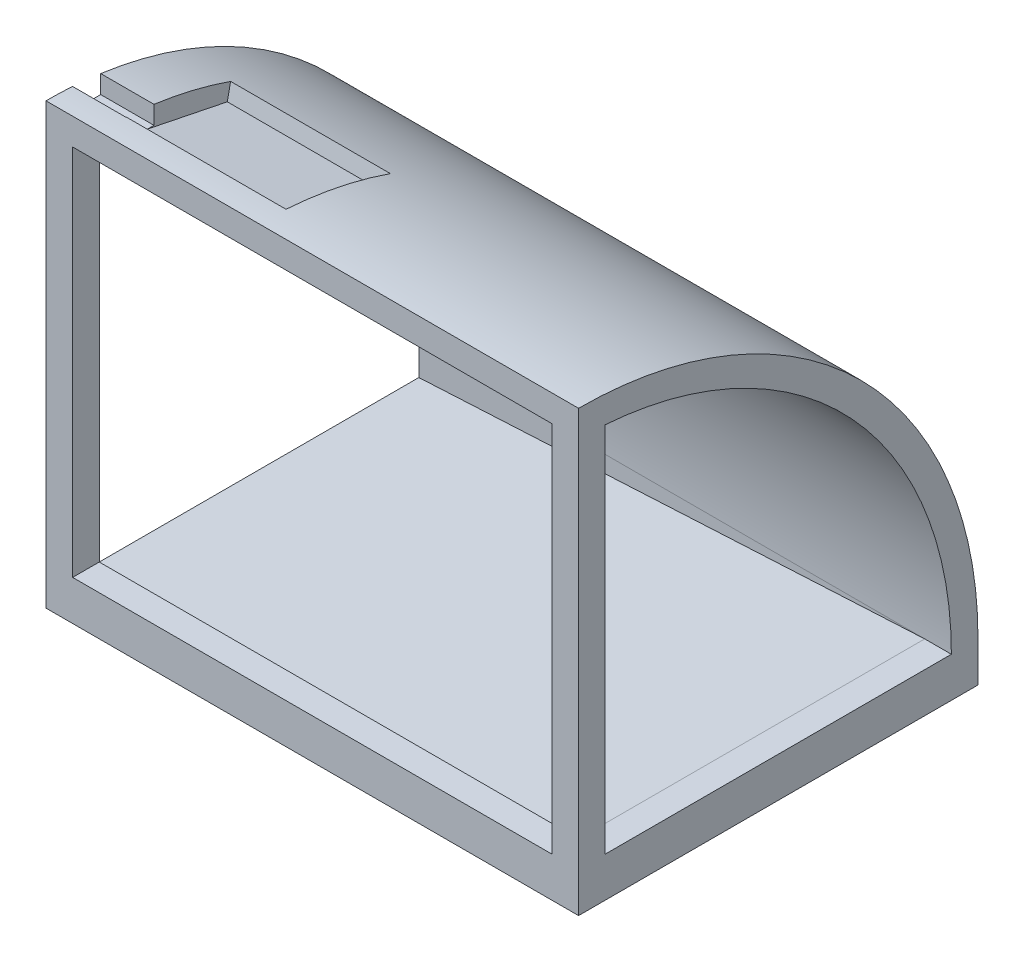
SolidWorks part; units mm, degrees
note: The reader was unsure of these and kept them because the rebuilt part matched: shared geometry of "Sketch1<5>", "Sketch1<6>".
ref_plane "Front Plane" through (0, 0, 0) normal (0, 0, 1) x (1, 0, 0)
ref_plane "Top Plane" through (0, 0, 0) normal (0, 1, 0) x (1, 0, 0)
ref_plane "Right Plane" through (0, 0, 0) normal (1, 0, 0) x (0, 0, -1)
sketch "Sketch1" plane through (0, 0, 0) normal (0, 1, 0) x (1, 0, 0)
  line L0 (-100, 65) -> (100, 65)
  line L3 (-100, 75) -> (100, 75)
  line L5 (-100, -75) -> (100, 75) construction
  line L6 (-100, 75) -> (100, -75) construction
  line L7 (-100, 75) -> (-100, 65)
  line L8 (100, 65) -> (100, 75)
  line L9 (-100, -15) -> (100, -15) construction
  line L10 (-100, 65) -> (100, 65)
  line L11 (-100, 65) -> (-100, -75)
  line L12 (-100, -75) -> (100, -75)
  line L13 (100, 65) -> (100, -75)
  line L14 (-100, -75) -> (-90, -75)
  line L15 (-100, -75) -> (-100, -65)
  line L16 (-100, -65) -> (-90, -65)
  line L17 (-90, -75) -> (-90, -65)
  line L18 (100, -75) -> (90, -75)
  line L19 (100, -75) -> (100, -65)
  line L20 (100, -65) -> (90, -65)
  line L21 (90, -75) -> (90, -65)
  point P0 (0, 0)
  dimension "D1" = 200
  dimension "D2" = 150
  dimension "D3" = 10
  dimension "D4" = 10
  dimension "D5" = 60
extrude "Boss-Extrude1" add sketch "Sketch1" against normal blind 15 contours L13 L0 L11 L12 | L0 L8 L3 L7 | L15 L14 L17 L16 | L19 L18 L21 L20
revolve "Revolve1" add sketch "Sketch1<5>" angle 90 about L12
sketch "Sketch1<5>" plane through (0, 0, 0) normal (0, 1, 0) x (1, 0, 0) same geometry as "Sketch1"
extrude "Boss-Extrude3" add sketch "Sketch1<6>" along normal up to surface (139.6424 mm away) contours L12 L17 L16 L11 | L21 L12 L13 L20
sketch "Sketch1<6>" plane through (0, 0, 0) normal (0, 1, 0) x (1, 0, 0) same geometry as "Sketch1"
sketch "Sketch4" plane through (0, 0, 65) normal (0, 0, 1) x (1, 0, 0)
  line L0 (-100, -10) -> (90, 0)
  line L1 (-90, 0) -> (90, 0) construction
  line L2 (-100, 0) -> (90, 0)
  line L5 (-100, -15) -> (-100, 150) construction
  line L6 (-100, -15) -> (-100, 150) construction
  line L7 (-100, 0) -> (-100, -10)
  point P1 (0, 0)
  point P7 (90, -0.3901)
  point P8 (0, 0)
  point P9 (0, 0)
  dimension "D1" = 5
extrude "Cut-Extrude1" cut sketch "Sketch4" against normal up to vertex (130 mm away)
ref_plane "Plane2" through (-80, 0, 0) normal (-1, 0, 0) x (0, 0, 1)
sketch "Sketch5" plane through (-80, 0, 0) normal (-1, 0, 0) x (0, 0, 1)
  line L2 (66.0959, 143.6209) -> (26.9041, 135.6209)
  line L3 (26.9041, 135.6209) -> (66.0959, 143.6209)
  line L4 (26.9041, 135.6209) -> (21.9041, 160.1158)
  line L5 (66.0959, 143.6209) -> (61.0959, 168.1158)
  line L6 (21.9041, 160.1158) -> (61.0959, 168.1158)
  line L7 (33.6353, 134.4434) -> (61.4034, 140.1115) construction
  arc A0 (65, 139.6424) -> (-65, 0) centre (75, 0) ccw construction
  arc A1 (75, 150) -> (-75, 0) centre (75, 0) ccw construction
  arc A2 (65, 139.6424) -> (-65, 0) centre (75, 0) ccw construction
  arc A3 (75, 150) -> (-75, 0) centre (75, 0) ccw construction
  point P3 (0, 0)
  dimension "D1" = 10
  dimension "D2" = 40
  dimension "D3" = 25
  dimension "D4" = 2.5
extrude "Cut-Extrude2" cut sketch "Sketch5" against normal blind 60 contours L2 L5 A2 L4 | L4 L6 L5 L2
sketch "Sketch7" plane through (-80, 0, 0) normal (-1, 0, 0) x (0, 0, 1)
  line L0 (54.454, 141.7519) -> (65, 141.7519)
  line L1 (65, 150) -> (54.454, 150)
  line L4 (54.454, 141.7519) -> (54.454, 150)
  line L5 (54.454, 150) -> (65, 150)
  line L6 (54.454, 150) -> (65, 150)
  line L7 (65, 141.7519) -> (65, 150)
  line L9 (54.454, 150) -> (54.454, 141.7519)
extrude "Cut-Extrude5" cut sketch "Sketch7" along normal blind 74 contours L0 L7 L1 L4
